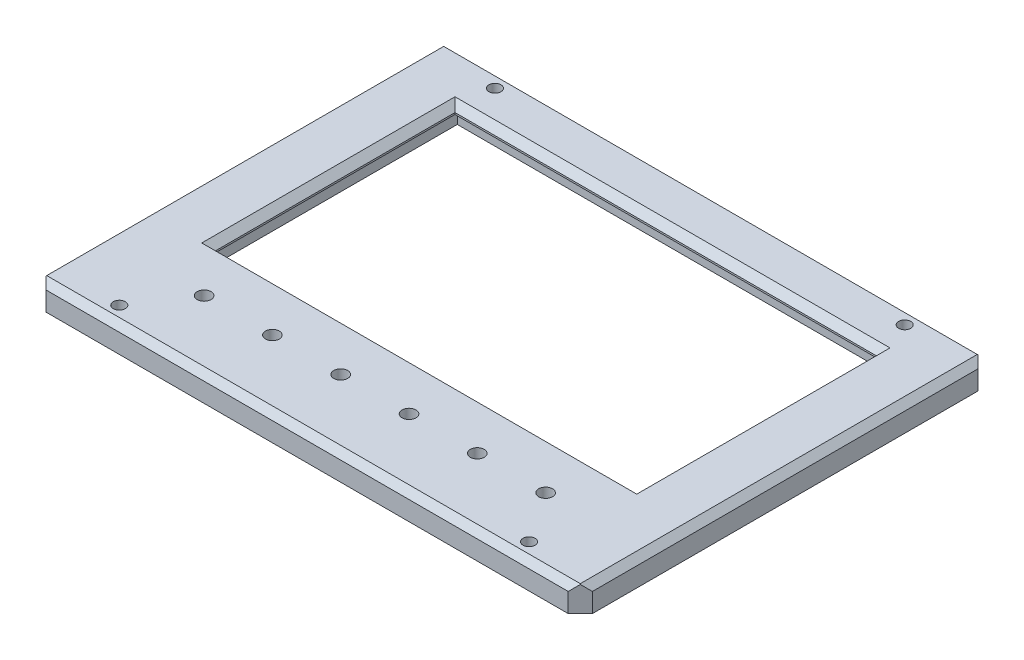
SolidWorks part; units mm, degrees
material "Mahogany"
ref_plane "Front Plane" through (0, 0, 0) normal (0, 0, 1) x (1, 0, 0)
ref_plane "Top Plane" through (0, 0, 0) normal (0, 1, 0) x (1, 0, 0)
ref_plane "Right Plane" through (0, 0, 0) normal (1, 0, 0) x (0, 0, -1)
sketch "Sketch1" plane through (0, 0, 0) normal (0, 1, 0) x (1, 0, 0)
  line L1 (-101.6, 76.2) -> (101.6, 76.2)
  line L2 (-101.6, 76.2) -> (-101.6, -76.2)
  line L3 (-101.6, -76.2) -> (101.6, -76.2)
  line L4 (101.6, 76.2) -> (101.6, -76.2)
  line L5 (-101.6, 76.2) -> (101.6, -76.2) construction
  line L6 (-101.6, -76.2) -> (101.6, 76.2) construction
  point P0 (0, 0)
  dimension "D1" = 203.2
  dimension "D2" = 152.4
extrude "Boss-Extrude1" add sketch "Sketch1" along normal blind 9.525
sketch "Sketch2" plane through (0, 9.525, 0) normal (0, 1, 0) x (1, 0, 0)
  line L0 (101.6, 76.2) -> (-101.6, 76.2) construction
  line L1 (-78.35, 57.15) -> (78.35, 57.15)
  line L2 (-78.35, 57.15) -> (-78.35, -31.95)
  line L3 (-78.35, -31.95) -> (78.35, -31.95)
  line L4 (78.35, 57.15) -> (78.35, -31.95)
  line L5 (-78.35, 57.15) -> (78.35, -31.95) construction
  line L6 (-78.35, -31.95) -> (78.35, 57.15) construction
  point P0 (0, 12.6)
  dimension "D1" = 156.7
  dimension "D2" = 89.1
  dimension "D3" = 19.05
extrude "Cut-Extrude1" cut sketch "Sketch2" against normal through all
chamfer "Chamfer1" distance 2.54 angle 45 4 edges at (78.35, 9.525, -12.6) (0, 9.525, 31.95) (-78.35, 9.525, -12.6) (0, 9.525, -57.15)
extrude "Cut-Extrude2" cut sketch "Sketch3" against normal blind 6.35
sketch "Sketch3" plane through (-44.7206, 0, -165.4534) normal (0, -1, 0) x (1, 0, 0)
  line L4 (-36.3394, 104.7334) -> (-36.3394, 204.7334)
  line L5 (128.5606, 104.7334) -> (-36.3394, 104.7334)
  line L6 (128.5606, 204.7334) -> (128.5606, 104.7334)
  line L7 (-36.3394, 204.7334) -> (128.5606, 204.7334)
sketch "Sketch4" plane through (0, 9.525, 0) normal (0, 1, 0) x (1, 0, 0)
  line L0 (-63.5, -51) -> (-38.1, -51) construction
  line L1 (-38.1, -51) -> (-12.7, -51) construction
  line L2 (-12.7, -51) -> (12.7, -51) construction
  line L3 (12.7, -51) -> (38.1, -51) construction
  line L4 (-78.35, -31.95) -> (78.35, -31.95) construction
  line L5 (38.1, -51) -> (63.5, -51) construction
  line L6 (-12.7, -51) -> (0, 0) construction
  line L7 (0, 0) -> (12.7, -51) construction
  circle A0 centre (-63.5, -51) radius 2.5797
  circle A1 centre (-38.1, -51) radius 2.5797
  circle A2 centre (-12.7, -51) radius 2.5797
  circle A3 centre (12.7, -51) radius 2.5797
  circle A4 centre (38.1, -51) radius 2.5797
  circle A5 centre (63.5, -51) radius 2.5797
  dimension "D1" = 5.1594
  dimension "D2" = 25.4
  dimension "D3" = 19.05
extrude "Cut-Extrude3" cut sketch "Sketch4" against normal through all
chamfer "Chamfer2" distance 2.3813 angle 45 4 edges at (101.6, 9.525, 0) (0, 9.525, 76.2) (0, 9.525, -76.2) (-101.6, 9.525, 0)
hole_wizard "#8 Clearance Hole1" positions "Sketch5" profile "Sketch6" hole size "#8" standard "ANSI Inch" end condition through all
sketch "Sketch5" plane through (0, 9.525, 0) normal (0, 1, 0) x (1, 0, 0)
  line L0 (-76.2, 69.85) -> (0, 0) construction
  line L1 (0, 0) -> (76.2, 69.85) construction
  line L3 (-101.6, 76.2) -> (101.6, 76.2) construction
  line L4 (101.6, -76.2) -> (-101.6, -76.2) construction
  point P0 (-76.2, 69.85)
  point P2 (76.2, 69.85)
  point P4 (76.2, -69.85)
  point P6 (-76.2, -69.85)
  dimension "D1" = 152.4
  dimension "D2" = 6.35
  dimension "D3" = 6.35
sketch "Sketch6" plane through (-76.2, 9.525, -69.85) normal (1, 0, 0) x (0, 0, 1)
  line L0 (0, 0) -> (0, 9.525)
  line L1 (0, 9.525) -> (2.2479, 9.525)
  line L2 (2.2479, 9.525) -> (2.2479, 0)
  line L5 (2.2479, 0) -> (0, 0)
  line L11 (0, -6.35) -> (0, 107.95) construction
  dimension "Thru Hole Dia." = 4.4958
  dimension "Thru Hole Depth" = 9.525
chamfer "Chamfer3" distance 4.4958 angle 45 4 edges at (101.6, 3.5719, -76.2) (-101.6, 3.5719, -76.2) (-101.6, 3.5719, 76.2) (101.6, 3.5719, 76.2)
